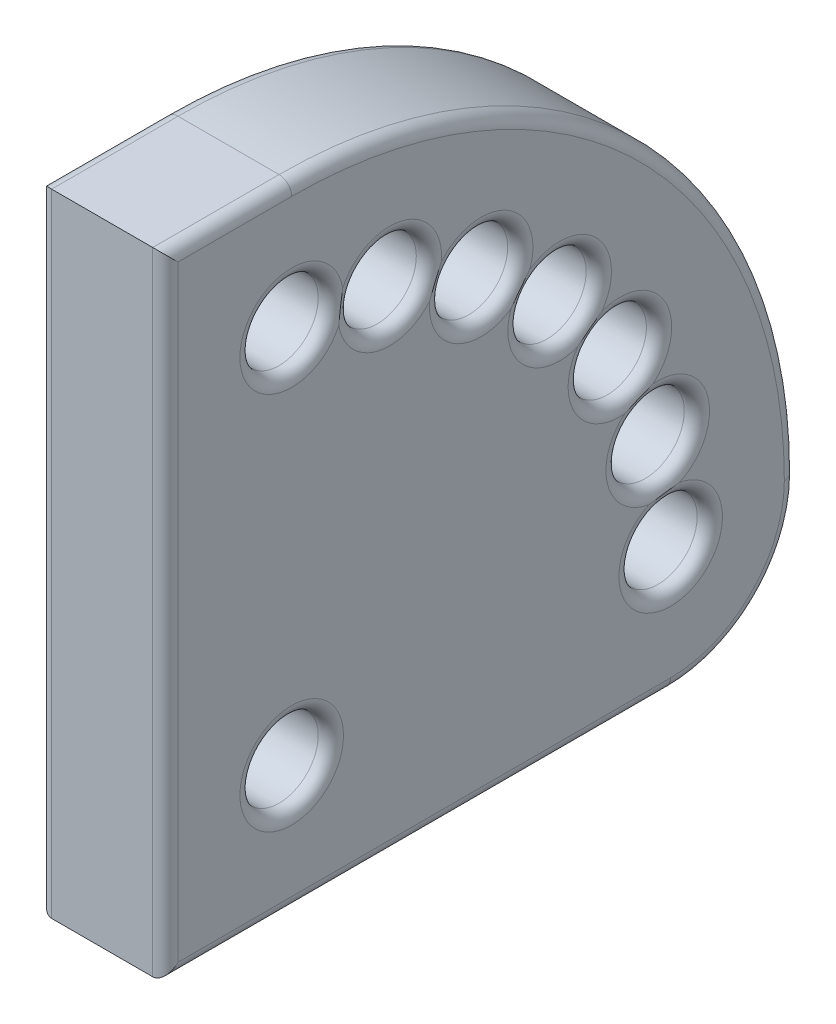
SolidWorks part; units mm, degrees
ref_plane "正面" through (0, 0, 0) normal (0, 0, 1) x (1, 0, 0)
ref_plane "平面" through (0, 0, 0) normal (0, 1, 0) x (1, 0, 0)
ref_plane "右側面" through (0, 0, 0) normal (1, 0, 0) x (0, 0, -1)
sketch "ｽｹｯﾁ1" plane through (0, 0, 0) normal (0, 0, 1) x (1, 0, 0)
  circle A0 centre (0, 0) radius 22.5
  circle A1 centre (0, 21) radius 1.55
  circle A2 centre (5.4352, 20.2844) radius 1.55
  circle A3 centre (10.5, 18.1865) radius 1.55
  circle A4 centre (14.8492, 14.8492) radius 1.55
  circle A5 centre (18.1865, 10.5) radius 1.55
  circle A6 centre (20.2844, 5.4352) radius 1.55
  circle A7 centre (21, 0) radius 1.55
  circle A8 centre (20.2844, -5.4352) radius 1.55
  circle A9 centre (18.1865, -10.5) radius 1.55
  circle A10 centre (14.8492, -14.8492) radius 1.55
  circle A11 centre (10.5, -18.1865) radius 1.55
  circle A12 centre (5.4352, -20.2844) radius 1.55
  circle A13 centre (0, -21) radius 1.55
  circle A14 centre (-5.4352, -20.2844) radius 1.55
  circle A15 centre (-10.5, -18.1865) radius 1.55
  circle A16 centre (-14.8492, -14.8492) radius 1.55
  circle A17 centre (-18.1865, -10.5) radius 1.55
  circle A18 centre (-20.2844, -5.4352) radius 1.55
  circle A19 centre (-21, 0) radius 1.55
  circle A20 centre (-20.2844, 5.4352) radius 1.55
  circle A21 centre (-18.1865, 10.5) radius 1.55
  circle A22 centre (-14.8492, 14.8492) radius 1.55
  circle A23 centre (-10.5, 18.1865) radius 1.55
  circle A24 centre (-5.4352, 20.2844) radius 1.55
  point P54 (0, 0)
  dimension "D1" = 21
  dimension "D2" = 3.1
  dimension "D3" = 45
  dimension "D4" = 24
extrude "ﾎﾞｽ - 押し出し1" add sketch "ｽｹｯﾁ1" along normal blind 5 rebuild error yes
sketch "ｽｹｯﾁ2" plane through (0, 0, 0) normal (0, 0, 1) x (1, 0, 0)
  line L1 (-2.5, 12.5) -> (2.5, 12.5)
  line L2 (-2.5, 12.5) -> (-2.5, -12.5)
  line L3 (-2.5, -12.5) -> (2.5, -12.5)
  line L4 (2.5, 12.5) -> (2.5, -12.5)
  line L5 (-2.5, 12.5) -> (2.5, -12.5) construction
  line L6 (-2.5, -12.5) -> (2.5, 12.5) construction
  point P0 (0, 0)
  dimension "D1" = 5
  dimension "D2" = 25
sketch "ｽｹｯﾁ5" plane through (0, 0, 0) normal (1, 0, 0) x (0, 0, -1)
  line L1 (0, 12.5) -> (5, 12.5)
  line L2 (0, 12.5) -> (0, -12.5)
  line L3 (0, -12.5) -> (5, -12.5)
  line L4 (5, 12.5) -> (5, -12.5)
  line L5 (0, -12.5) -> (25, -12.5)
  line L6 (0, -12.5) -> (0, -7.5)
  line L7 (0, -7.5) -> (25, -7.5)
  line L8 (25, -12.5) -> (25, -7.5)
  arc A0 (5, 12.5) -> (25, -7.5) centre (5, -7.5) cw
  circle A1 centre (5, -7.5) radius 1.55
  circle A2 centre (5, 7.5) radius 1.55
  circle A3 centre (8.8823, 6.9889) radius 1.55
  circle A4 centre (12.5, 5.4904) radius 1.55
  circle A5 centre (15.6066, 3.1066) radius 1.55
  circle A6 centre (17.9904, 0) radius 1.55
  circle A7 centre (19.4889, -3.6177) radius 1.55
  circle A8 centre (20, -7.5) radius 1.55
  point P25 (5, -7.5)
  dimension "D4" = 3.1
  dimension "D5" = 3.1
  dimension "D6" = 15
  dimension "D1" = 5
  dimension "D2" = 5
  dimension "D3" = 25
  dimension "D7" = 7
extrude "ﾎﾞｽ - 押し出し3" add sketch "ｽｹｯﾁ5" along normal mid plane 5 contours A0 L4 L7 | L2 L7 L4 L1 | L5 L8 L7 L4 | L7 L2 L3 L4 region at (0, 2.4868, -2.3895) region at (0, 0.8636, -13.3636) region at (0, -10.1504, -2.3496) region at (0, -10.1105, -14.9868)
fillet "ﾌｨﾚｯﾄ1" radius 5 1 edges at (0, -12.5, -25)
fillet "ﾌｨﾚｯﾄ2" radius 0.5 26 edges at (2.5, 6.9889, -10.4323) (2.5, 5.4904, -14.05) (2.5, 3.1066, -17.1566) (2.5, 0, -19.5404) (2.5, -3.6177, -21.0389) (2.5, -7.5, -21.55) (2.5, 7.5, -6.55) (2.5, 12.5, -2.5) (2.5, 6.6421, -19.1421) (2.5, -11.0355, -23.5355) (2.5, -12.5, -10) (2.5, -7.5, -6.55) (-2.5, 6.9889, -10.4323) (-2.5, 5.4904, -14.05) (-2.5, 3.1066, -17.1566) (-2.5, 0, -19.5404) (-2.5, -3.6177, -21.0389) (-2.5, -7.5, -21.55) (-2.5, 7.5, -6.55) (-2.5, 12.5, -2.5) (-2.5, -12.5, -10) (-2.5, -11.0355, -23.5355) (-2.5, 6.6421, -19.1421) (-2.5, -7.5, -6.55) (2.5, 0, 0) (-2.5, 0, 0)
